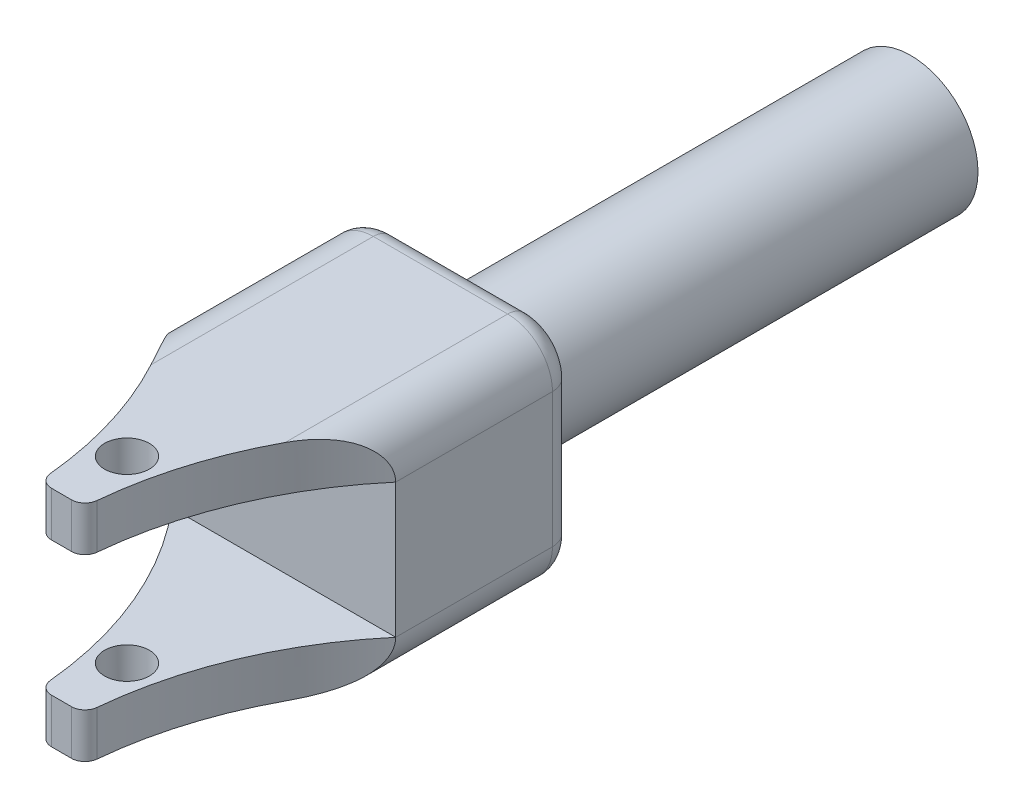
SolidWorks part; units mm, degrees
ref_plane "Front Plane" through (0, 0, 0) normal (0, 0, 1) x (1, 0, 0)
ref_plane "Top Plane" through (0, 0, 0) normal (0, 1, 0) x (1, 0, 0)
ref_plane "Right Plane" through (0, 0, 0) normal (1, 0, 0) x (0, 0, -1)
sketch "Sketch2" plane through (0, 0, 0) normal (0, 0, 1) x (1, 0, 0)
  circle A0 centre (0, 0) radius 15
  dimension "D1" = 30
extrude "Boss-Extrude2" add sketch "Sketch2" along normal blind 140 contours A0
ref_plane "Plane1" through (0, 0, 100) normal (0, 0, 1) x (1, 0, 0)
sketch "Sketch4" plane through (0, 0, 100) normal (0, 0, 1) x (1, 0, 0)
  line L1 (-25, 25) -> (25, 25)
  line L2 (-25, 25) -> (-25, -25)
  line L3 (-25, -25) -> (25, -25)
  line L4 (25, 25) -> (25, -25)
  line L5 (-25, 25) -> (25, -25) construction
  line L6 (-25, -25) -> (25, 25) construction
  point P0 (0, 0)
  dimension "D1" = 50
  dimension "D2" = 50
extrude "Boss-Extrude3" add sketch "Sketch4" along normal blind 89.61
fillet "Fillet1" radius 5 4 edges at (-25, 0, 100) (0, -25, 100) (25, 0, 100) (0, 25, 100)
fillet "Fillet3" radius 10 8 edges at (23.5355, -23.5355, 101.4645) (23.5355, 23.5355, 101.4645) (-23.5355, 23.5355, 101.4645) (-23.5355, -23.5355, 101.4645) (-25, -25, 147.305) (-25, 25, 147.305) (25, 25, 147.305) (25, -25, 147.305)
sketch "Sketch6" plane through (0, 0, 0) normal (1, 0, 0) x (0, 0, -1)
  line L0 (-189.61, 15) -> (-189.61, -15) construction
  line L1 (-140, 15) -> (-189.61, 15)
  line L2 (-140, 15) -> (-140, -15)
  line L3 (-140, -15) -> (-189.61, -15)
  line L4 (-189.61, 15) -> (-189.61, -15)
  line L5 (-140, 15) -> (-189.61, -15) construction
  line L6 (-140, -15) -> (-189.61, 15) construction
  point P0 (-164.805, 0)
  point P7 (0, 0)
  dimension "D1" = 49.61
  dimension "D2" = 30
extrude "Cut-Extrude1" cut sketch "Sketch6" against normal mid plane 89.61
sketch "Sketch7" plane through (0, 0, 0) normal (0, 1, 0) x (1, 0, 0)
  line L0 (-15, -189.61) -> (15, -189.61) construction
  line L1 (15, -100) -> (-15, -100) construction
  line L3 (-2.2289, -189.61) -> (2.2289, -189.61)
  line L4 (25, -140) -> (24.9794, -140.4996)
  circle A0 centre (0, -175) radius 5
  arc A1 (-5.2153, -186.8951) -> (-2.2289, -189.61) centre (-2.2289, -186.61) ccw
  arc A2 (-25, -140) -> (-5.2153, -186.8951) centre (-89.8307, -194.9726) cw
  arc A3 (25, -140) -> (5.2153, -186.8951) centre (89.8307, -194.9726) ccw
  arc A4 (5.2153, -186.8951) -> (2.2289, -189.61) centre (2.2289, -186.61) cw
  arc A5 (-25, -140) -> (25, -140) centre (0, -169.4832) ccw
  point P2 (0, -189.61)
  point P16 (-5, -189.61)
  point P19 (-11.5152, -161.9319)
  point P22 (5, -189.61)
  dimension "D1" = 10
  dimension "D2" = 10
  dimension "D3" = 85
  dimension "D4" = 85
  dimension "D6" = 3
  dimension "D7" = 3
  dimension "D5" = 75
extrude "Cut-Extrude5" cut sketch "Sketch7" against normal through all both and the other way through all contours A0 | A3 A4 L3 A1 A2 A5
